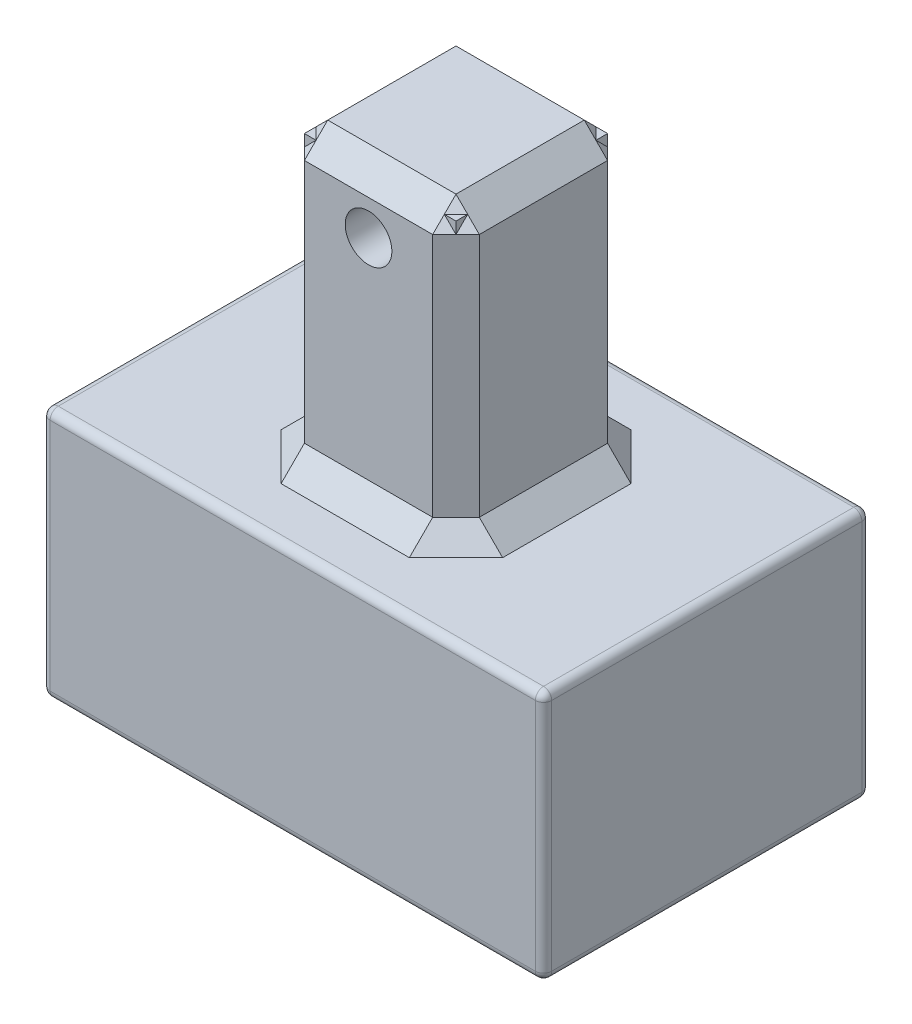
SolidWorks part; units mm, degrees
ref_plane "Front Plane" through (0, 0, 0) normal (0, 0, 1) x (1, 0, 0)
ref_plane "Top Plane" through (0, 0, 0) normal (0, 1, 0) x (1, 0, 0)
ref_plane "Right Plane" through (0, 0, 0) normal (1, 0, 0) x (0, 0, -1)
sketch "Sketch1" plane through (0, 0, 0) normal (0, 0, 1) x (1, 0, 0)
  line L1 (-35.5233, 0) -> (-27.3134, 0)
  line L2 (-24.7734, 0) -> (-27.3134, 0)
  line L3 (-24.7734, 0) -> (-24.1384, 0)
  line L4 (-24.1384, 0) -> (-21.5984, 0)
  line L5 (-21.5984, 0) -> (-18.4234, 0)
  line L6 (18.4234, 0) -> (-18.4234, 0)
  line L7 (18.4234, 0) -> (21.5984, 0)
  line L8 (24.1384, 0) -> (21.5984, 0)
  line L9 (24.7734, 0) -> (24.1384, 0)
  line L10 (27.3134, 0) -> (24.7734, 0)
  line L11 (0, 27.3134) -> (27.3134, 27.3134)
  line L12 (27.3134, 27.3134) -> (27.3134, 0)
  line L13 (0, 27.3134) -> (-27.3134, 27.3134)
  line L14 (-27.3134, 27.3134) -> (-27.3134, 0)
  arc A7 (24.7734, 0) -> (-24.7734, 0) centre (0, 0) ccw
  arc A8 (18.4234, 0) -> (-18.4234, 0) centre (0, 0) ccw
  arc A11 (21.5984, 0) -> (-21.5984, 0) centre (0, 0) ccw
  arc A12 (24.1384, 0) -> (-24.1384, 0) centre (0, 0) ccw
  arc A13 (27.3134, 0) -> (-27.3134, 0) centre (0, 0) ccw
  dimension "D5" = 43.1967
  dimension "D6" = 36.8467
  dimension "D7" = 54.6267
  dimension "D1" = 48.2767
  dimension "D2" = 49.5467
extrude "Main Body Extrude" add sketch "Sketch1" along normal mid plane 35.56 contours L6 A8 | L7 A11 L5 A8 | L8 A12 L4 A11 | A12 L9 A7 L3 | L10 A13 L2 A7 | A13 L13 L14 | A13 L12 L11 region at (0, 24.2194, 0) region at (-26.0434, 0.6107, 0) region at (-21.2124, 21.2124, 0) region at (0, 23.5986, 0) region at (21.2124, 21.2124, 0) region at (0, 21.1154, 0) region at (0, 7.8191, 0)
sketch "Sketch5" plane through (0, 27.3134, 0) normal (0, 1, 0) x (1, 0, 0)
  line L0 (27.3134, 0) -> (-27.3134, 0) construction
  line L1 (0, -17.78) -> (0, 17.78) construction
  line L3 (-9.525, -9.525) -> (9.525, -9.525)
  line L4 (27.3134, 17.78) -> (-27.3134, 17.78)
  line L5 (-27.3134, 17.78) -> (-27.3134, -17.78)
  line L6 (-27.3134, -17.78) -> (27.3134, -17.78)
  line L7 (27.3134, -17.78) -> (27.3134, 17.78)
  line L8 (27.3134, 17.78) -> (-27.3134, 17.78)
  line L9 (-27.3134, 17.78) -> (-27.3134, -17.78)
  line L10 (-27.3134, -17.78) -> (27.3134, -17.78)
  line L11 (27.3134, -17.78) -> (27.3134, 17.78)
  line L12 (-9.525, -9.525) -> (-9.525, 9.525)
  line L13 (-9.525, 9.525) -> (9.525, 9.525)
  line L14 (9.525, -9.525) -> (9.525, 9.525)
  line L15 (-9.525, -9.525) -> (9.525, 9.525) construction
  line L16 (-9.525, 9.525) -> (9.525, -9.525) construction
  point P8 (0, 0)
  dimension "D2" = 19.05
  dimension "D3" = 19.05
  dimension "D1" = 0
extrude "Tibia Connection Extrude" add sketch "Sketch5" along normal blind 31.75 contours L3 L14 L13 L12 region at (0, 27.3134, 0)
sketch "Sketch6" plane through (0, 0, 9.525) normal (0, 0, 1) x (1, 0, 0)
  line L0 (0, 59.0634) -> (0, 52.7134)
  line L4 (-9.525, 27.3134) -> (9.525, 27.3134)
  line L5 (9.525, 27.3134) -> (9.525, 59.0634)
  line L6 (9.525, 59.0634) -> (-9.525, 59.0634)
  line L7 (-9.525, 59.0634) -> (-9.525, 27.3134)
  line L8 (-9.525, 27.3134) -> (9.525, 27.3134)
  line L9 (9.525, 27.3134) -> (9.525, 59.0634)
  line L10 (9.525, 59.0634) -> (-9.525, 59.0634)
  line L11 (-9.525, 59.0634) -> (-9.525, 27.3134)
  circle A0 centre (0, 52.7134) radius 2.54
  dimension "D3" = 5.08
  dimension "D2" = 6.35
  dimension "D1" = 0
extrude "Pinhole Cut" cut sketch "Sketch6" against normal blind 25.4 contours A0
shell "Hinge Shell" thickness 1.27 removed face at (0, 0, 0)
extrude "Groove 1" cut sketch "Sketch1<13>" against normal blind 1.27 from surface contours L7 A11 L5 A8 region at (0, 21.1154, 0) starting at face at (0, 13.0217, -15.24)
sketch "Sketch1<13>" plane through (0, 0, 0) normal (0, 0, 1) x (1, 0, 0) same geometry as "Sketch1"
extrude "Groove 2" cut sketch "Sketch1<14>" along normal blind 1.27 from surface contours L7 A11 L5 A8 region at (0, 21.1154, 0) starting at face at (0, 13.0217, 15.24)
sketch "Sketch1<14>" plane through (0, 0, 0) normal (0, 0, 1) x (1, 0, 0) same geometry as "Sketch1"
fillet "Fillet1" radius 0.889 12 edges at (0, 0, -17.78) (27.3134, 13.6567, -17.78) (0, 27.3134, -17.78) (-27.3134, 13.6567, -17.78) (0, 0, 17.78) (0, 27.3134, 17.78) (-27.3134, 13.6567, 17.78) (-27.3134, 0, 0) (-27.3134, 27.3134, 0) (27.3134, 27.3134, 0) (27.3134, 0, 0) (27.3134, 13.6567, 17.78)
chamfer "Chamfer1" distance 2.54 angle 45 12 edges at (9.525, 59.0634, 0) (9.525, 43.1884, 9.525) (0, 59.0634, 9.525) (-9.525, 43.1884, 9.525) (-9.525, 59.0634, 0) (-9.525, 43.1884, -9.525) (0, 59.0634, -9.525) (9.525, 43.1884, -9.525) (9.525, 27.3134, 0) (0, 27.3134, -9.525) (-9.525, 27.3134, 0) (0, 27.3134, 9.525)
equation "\"InnerBaseDiameter\"=0.98"
equation "\"InnerBaseOuterGroove\"= \"InnerBaseDiameter\" - 0.1"
equation "\"InnerHingeInnerCurve\"= 1"
equation "\"InnerHingeOuterCurve\"= \"InnerHingeInnerCurve\" + 0.1"
equation "\"InnerBaseInnerGroove\"= \"InnerBaseOuterGroove\" - 0.1"
equation "\"InnerHingeWidth\"= 1.45"
equation "\"OuterBaseInnerGroove\"= \"OuterBaseOuterGroove\" - 0.25"
equation "\"OuterBaseDiameter\"= ( ( \"InnerHingeOuterCurve\" / 2 ) ^ 2 + ( \"InnerHingeLength\" / 2 ) ^ 2 ) ^ 0.5 * 2"
equation "\"InnerHingeLength\"=1.55"
equation "\"OuterBaseOuterGroove\"= \"OuterBaseDiameter\" - 0.2"
equation "\"D5@Sketch1\"=\"OuterBaseOuterGroove\""
equation "\"D6@Sketch1\"=\"OuterBaseInnerGroove\""
equation "\"OuterHingeOuterDiameter\"= \"OuterHingeInnerDiameter\" + 0.2"
equation "\"D1@Sketch1\"=\"OuterBaseDiameter\""
equation "\"OuterHingeInnerDiameter\"= \"OuterBaseDiameter\" + 0.05"
equation "\"D7@Sketch1\"=\"OuterHingeOuterDiameter\""
equation "\"D2@Sketch1\"=\"OuterHingeInnerDiameter\""
equation "\"OuterHingeLength\"= \"InnerHingeOuterCurve\" + 0.3"
equation "\"D1@Main Body Extrude\" = \"OuterHingeLength\""
equation "\"TibiaConnectionLength\"=1.25"
equation "\"D1@Tibia Connection Extrude\"=\"TibiaConnectionLength\""
equation "\"D1@Boss-Extrude2\"=\"BaseWidth\"+0.095"
equation "\"D1@Boss-Extrude1\"=\"BaseWidth\""
equation "\"D6@Sketch1\"=\"BaseHeight\""
